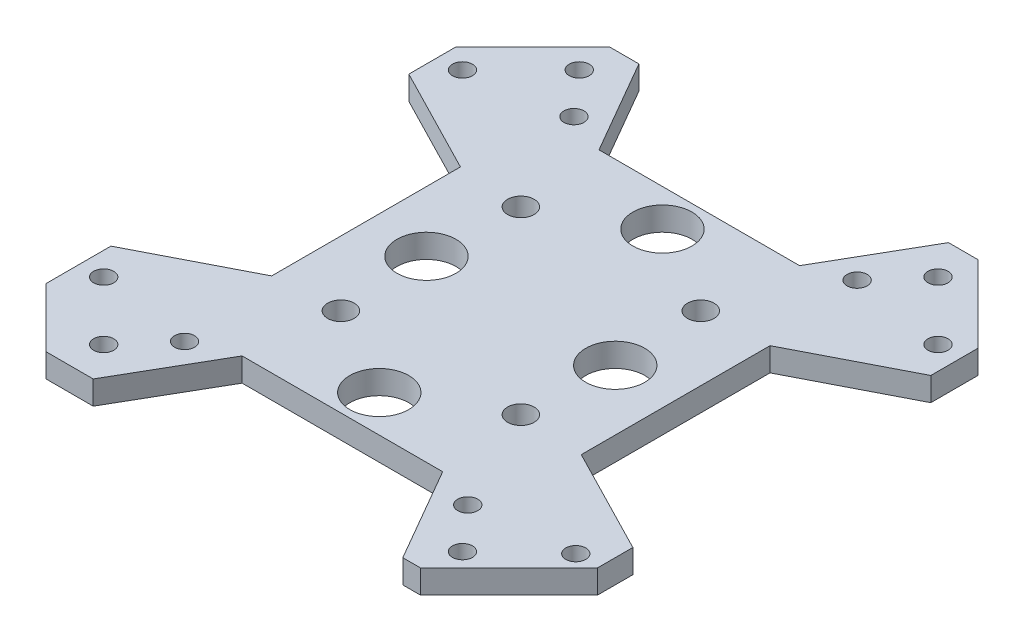
SolidWorks part; units mm, degrees
material "Thornel Mat VMA"
ref_plane "前视基准面" through (0, 0, 0) normal (0, 0, 1) x (1, 0, 0)
ref_plane "上视基准面" through (0, 0, 0) normal (0, 1, 0) x (1, 0, 0)
ref_plane "右视基准面" through (0, 0, 0) normal (1, 0, 0) x (0, 0, -1)
other "Configuration Table"
sketch "草图1" plane through (0, 0, 0) normal (0, 1, 0) x (1, 0, 0)
  line L8 (-40.3051, 30.4056) -> (-30.4056, 40.3051) construction
  line L9 (0, 0) -> (75.4458, 0) construction
  line L10 (0, 0) -> (0, 38.6741) construction
  line L21 (44.2385, 33.25) -> (44.2385, 25.25)
  line L22 (-44.2385, 33.25) -> (-44.2385, 25.25)
  line L23 (-34.2385, -46.25) -> (-26.2385, -46.25)
  line L24 (-31.2385, 46.25) -> (-26.2385, 46.25)
  line L25 (-44.2385, 33.25) -> (-31.2385, 46.25)
  line L26 (31.2385, 46.25) -> (44.2385, 33.25)
  line L27 (29.2385, -46.25) -> (44.2385, -31.25)
  line L28 (-44.2385, -36.25) -> (-34.2385, -46.25)
  line L30 (-26.2385, 16) -> (-26.2385, -16)
  line L32 (-44.2385, -25.25) -> (-44.2385, -36.25)
  line L33 (-44.2385, 25.25) -> (-26.2385, 16)
  line L34 (-44.2385, -25.25) -> (-26.2385, -16)
  line L35 (44.2385, -25.25) -> (26.2385, -16)
  line L36 (26.2385, 16) -> (26.2385, -16)
  line L37 (44.2385, 25.25) -> (26.2385, 16)
  line L38 (44.2385, -25.25) -> (44.2385, -31.25)
  line L39 (-26.2385, 46.25) -> (-17, 30.2485)
  line L40 (-17, 30.2485) -> (17, 30.2485)
  line L41 (26.2385, 46.25) -> (17, 30.2485)
  line L42 (26.2385, 46.25) -> (31.2385, 46.25)
  line L43 (26.2385, -46.25) -> (17, -30.2485)
  line L44 (-17, -30.2485) -> (17, -30.2485)
  line L45 (-26.2385, -46.25) -> (-17, -30.2485)
  line L46 (26.2385, -46.25) -> (29.2385, -46.25)
  circle A0 centre (-15.25, -15.25) radius 2.25
  circle A1 centre (-15.25, 15.25) radius 2.25
  circle A2 centre (15.25, -15.25) radius 2.25
  circle A3 centre (15.25, 15.25) radius 2.25
  circle A4 centre (-24, -33) radius 1.7
  circle A9 centre (-16, 0) radius 5
  circle A10 centre (0, 24) radius 5
  circle A13 centre (-30.4056, -40.3051) radius 1.7
  circle A14 centre (-30.4056, 40.3051) radius 1.7
  circle A15 centre (-40.3051, 30.4056) radius 1.7
  circle A16 centre (30.4056, -40.3051) radius 1.7
  circle A17 centre (40.3051, -31) radius 1.6949
  circle A18 centre (40.3051, 30.4056) radius 1.6949
  circle A19 centre (30.4056, 40.3051) radius 1.7
  circle A20 centre (-40.3051, -30.4056) radius 1.7
  circle A21 centre (24, -33) radius 1.7
  circle A22 centre (24, 33) radius 1.7
  circle A23 centre (-24, 33) radius 1.7
  circle A24 centre (16, 0) radius 5
  circle A25 centre (0, -24) radius 5
  point P1 (-44.2385, -46.25)
  point P7 (-44.2385, 46.25)
  point P57 (44.2385, 46.25)
  point P58 (44.2385, -46.25)
  point P61 (-26.2385, 0)
  point P70 (0, 30.2485)
  dimension "D3" = 4.5
  dimension "D4" = 4.5
  dimension "D14" = 3.4
  dimension "D21" = 10
  dimension "D22" = 10
  dimension "D2" = 46.25
  dimension "D5" = 44.2385
  dimension "D6" = 60
  dimension "D7" = 18
  dimension "D9" = 24
  dimension "D10" = 16
  dimension "D11" = 40.3051
  dimension "D12" = 24
  dimension "D13" = 33
  dimension "D17" = 8
  dimension "D18" = 16
  dimension "D19" = 5
  dimension "D20" = 17
extrude "凸台-拉伸1" add sketch "草图1" along normal blind 4
